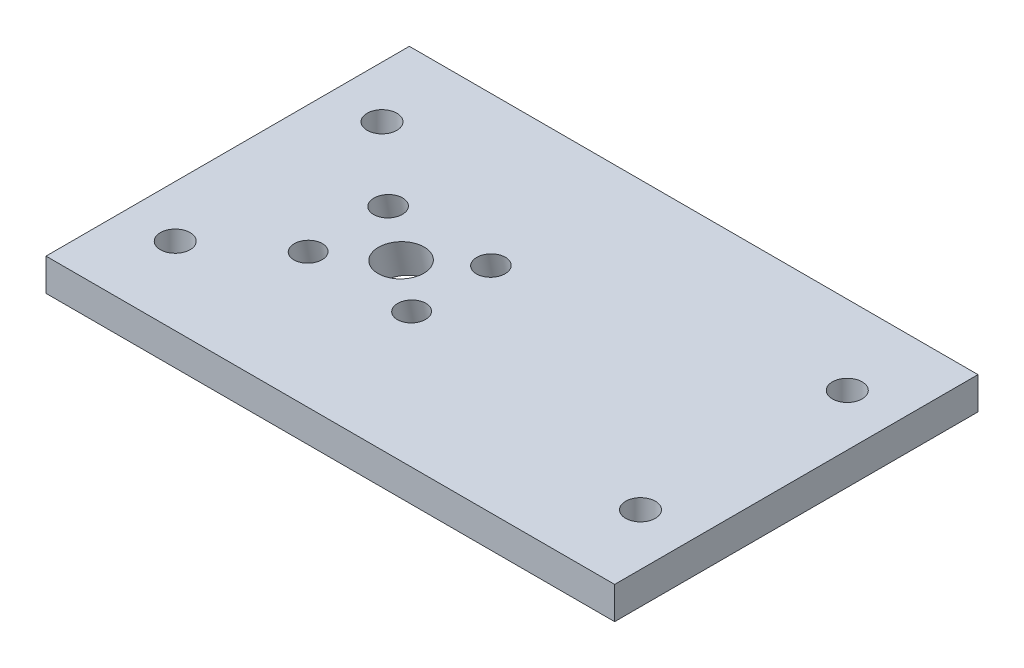
SolidWorks part; units mm, degrees
ref_plane "Front" through (0, 0, 0) normal (0, 0, 1) x (1, 0, 0)
ref_plane "Top" through (0, 0, 0) normal (0, 1, 0) x (1, 0, 0)
ref_plane "Right" through (0, 0, 0) normal (1, 0, 0) x (0, 0, -1)
sketch "Sketch1" plane through (0, 0, 0) normal (0, 1, 0) x (1, 0, 0)
  line L1 (0, 0) -> (90, 0)
  line L2 (0, 0) -> (0, 56.23)
  line L3 (0, 56.23) -> (90, 56.23)
  line L4 (90, 0) -> (90, 56.23)
  dimension "D1" = 90
  dimension "D2" = 56.23
extrude "Boss-Extrude1" add sketch "Sketch1" along normal blind 5
sketch "Sketch2" plane through (0, 5, 0) normal (0, 1, 0) x (1, 0, 0)
  circle A0 centre (82, 12) radius 2.3
  circle A1 centre (10, 12) radius 2.3
extrude "Cut-Extrude1" cut sketch "Sketch2" against normal blind 15
sketch "Sketch4" plane through (0, 5, 0) normal (0, 1, 0) x (1, 0, 0)
  circle A0 centre (39.2121, 27.5705) radius 2.2
  circle A1 centre (23.8176, 32.2728) radius 2.2
  circle A2 centre (43.572, 44.174) radius 2.2
  circle A3 centre (28.1775, 48.8763) radius 2.2
ref_plane "Plane1" through (0, 4.818, 0.9365) normal (0, 0.9816, 0.1908) x (1, 0, 0)
sketch "Sketch6" plane through (0, 4.818, 0.9365) normal (0, 0.9816, 0.1908) x (1, 0, 0)
  circle A0 centre (28.1775, 48.9324) radius 2.0398
  circle A1 centre (23.8176, 32.6339) radius 2.0398
  circle A2 centre (39.2121, 28.018) radius 2.0398
  circle A3 centre (43.572, 44.3165) radius 2.0398
sketch "Sketch7" plane through (0, 5, 0) normal (0, 1, 0) x (1, 0, 0)
  circle A0 centre (82, 44) radius 2.3
  circle A1 centre (10, 44) radius 2.3
extrude "Cut-Extrude3" cut sketch "Sketch7" against normal blind 45
sketch "Sketch8" plane through (0, 0, 0) normal (-1, 0, 0) x (0, 0, 1)
  circle A0 centre (-29.8532, 2.0033) radius 1.2661
sketch "Sketch9" plane through (0, 0, 0) normal (-1, 0, 0) x (0, 0, 1)
  line L1 (-56.23, 0) -> (4.9539, 0)
  line L2 (-56.23, 0) -> (-56.23, 5.0439)
  line L3 (-56.23, 5.0439) -> (4.9539, 5.0439)
  line L4 (4.9539, 0) -> (4.9539, 5.0439)
extrude "Cut-Extrude4" cut sketch "Sketch9" against normal blind 2
sketch "Sketch10" plane through (0, 0, 0) normal (0, -1, 0) x (-1, 0, 0)
  circle A0 centre (-21.7903, 34.1259) radius 2.2
  circle A1 centre (-37.7005, 34.1259) radius 2.2
  circle A2 centre (-21.7903, 50.1487) radius 2.2
  circle A3 centre (-37.7005, 50.1487) radius 2.2
sketch "Sketch11" plane through (0, 4.818, 0.9365) normal (0, 0.9816, 0.1908) x (1, 0, 0)
  circle A0 centre (21.7903, 49.2273) radius 2.1596
  circle A1 centre (37.7005, 49.2273) radius 2.2
  circle A2 centre (37.7005, 33.499) radius 2.2001
  circle A3 centre (21.7903, 33.499) radius 2.1596
sketch "Sketch12" plane through (0, 0, 0) normal (0, -1, 0) x (-1, 0, 0)
  circle A0 centre (-21.699, 21.8394) radius 2.2
  circle A1 centre (-21.699, 38.1497) radius 2.2
  circle A2 centre (-37.7096, 21.8394) radius 2.2
  circle A3 centre (-37.7096, 38.1497) radius 2.2
sketch "Sketch13" plane through (0, 4.818, 0.9365) normal (0, 0.9816, 0.1908) x (1, 0, 0)
  circle A0 centre (21.7903, 33.499) radius 2.2
  circle A1 centre (37.7005, 33.499) radius 2.2
  circle A2 centre (21.699, 21.4382) radius 2.1596
  circle A3 centre (37.7096, 21.4382) radius 2.1596
  circle A4 centre (30.0367, 27.3722) radius 3.5
extrude "Cut-Extrude5" cut sketch "Sketch13" against normal blind 20
